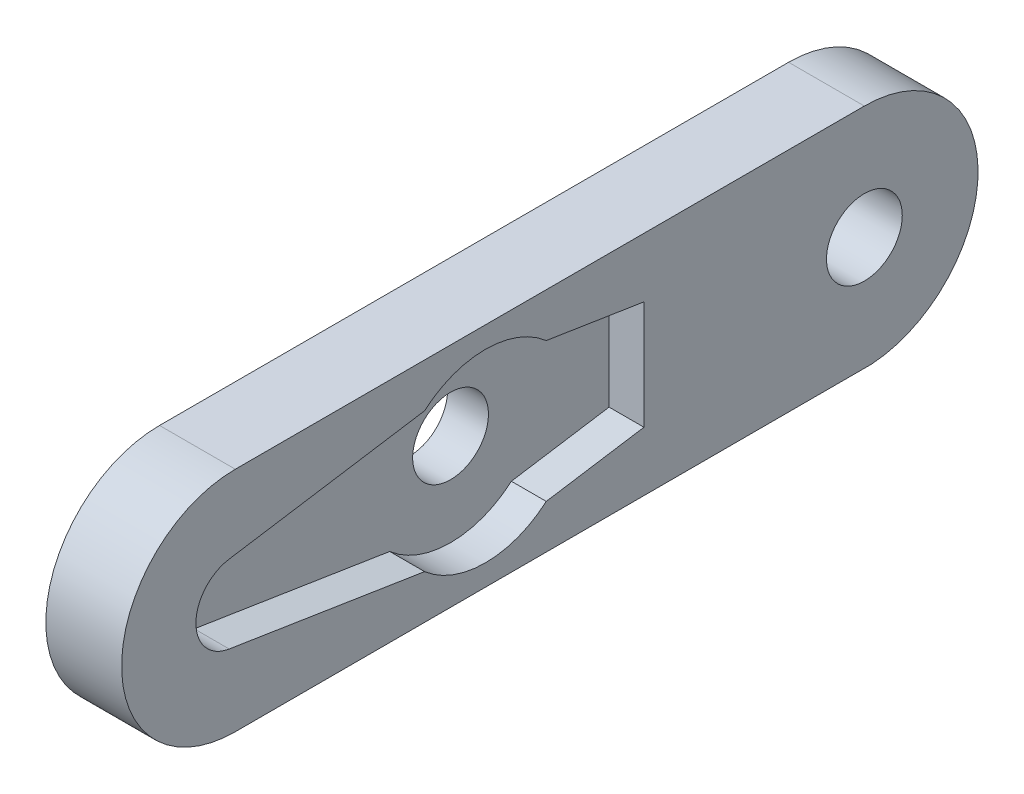
SolidWorks part; units mm, degrees
note: The reader was unsure of these and kept them because the rebuilt part matched: shared geometry of "Sketch4<3>".
ref_plane "Front Plane" through (0, 0, 0) normal (0, 0, 1) x (1, 0, 0)
ref_plane "Top Plane" through (0, 0, 0) normal (0, 1, 0) x (1, 0, 0)
ref_plane "Right Plane" through (0, 0, 0) normal (1, 0, 0) x (0, 0, -1)
sketch "Sketch1" plane through (0, 0, 0) normal (1, 0, 0) x (0, 0, -1)
  line L4 (10.4582, 3.5814) -> (4.0128, 4.5943)
  line L5 (-4.0128, 4.5943) -> (-16.9036, 2.5685)
  line L6 (-16.9036, -2.5685) -> (-4.0128, -4.5943)
  line L7 (4.0128, -4.5943) -> (10.4582, -3.5814)
  line L8 (0, 0) -> (20, 0)
  line L9 (10.4582, 3.5814) -> (10.4582, -3.5814)
  line L10 (-16.5, 7.5) -> (20, 7.5)
  line L11 (-16.5, -7.5) -> (20.4815, -7.4845)
  arc A4 (4.0128, 4.5943) -> (-4.0128, 4.5943) centre (0, 0) ccw
  arc A5 (-16.9036, 2.5685) -> (-16.9036, -2.5685) centre (-16.5, 0) ccw
  arc A6 (-4.0128, -4.5943) -> (4.0128, -4.5943) centre (0, 0) ccw
  circle A8 centre (20, 0) radius 2.5
  circle A9 centre (20, 0) radius 7.5
  arc A10 (-16.5, 7.5) -> (-9.954, -3.6606) centre (-16.5, 0) ccw
  dimension "D1" = 5
extrude "Boss-Extrude1" add sketch "Sketch1" along normal blind 2.3
sketch "Sketch2" plane through (0, 0, 0) normal (-1, 0, 0) x (0, 0, 1)
  line L2 (16.5, 7.5) -> (-20, 7.5)
  line L3 (-20.4815, -7.4845) -> (16.5, -7.5)
  line L4 (16.5, 7.5) -> (-20, 7.5)
  line L5 (-20.4815, -7.4845) -> (16.5, -7.5)
  circle A0 centre (-20, 0) radius 2.5 construction
  circle A1 centre (-20, 0) radius 2.5
  arc A2 (16.5, -7.5) -> (16.5, 7.5) centre (16.5, 0) ccw
  arc A3 (-20, 7.5) -> (-20.4815, -7.4845) centre (-20, 0) ccw
  arc A4 (16.5, -7.5) -> (16.5, 7.5) centre (16.5, 0) ccw
  arc A5 (-20, 7.5) -> (-20.4815, -7.4845) centre (-20, 0) ccw
  dimension "D1" = 0
extrude "Boss-Extrude2" add sketch "Sketch2" along normal blind 2.7
sketch "Sketch3" plane through (0, 0, 0) normal (1, 0, 0) x (0, 0, -1)
  circle A0 centre (0, 0) radius 2.5
extrude "Cut-Extrude1" cut sketch "Sketch3" against normal blind 10
sketch "Sketch4" plane through (2.3, 0, 0) normal (1, 0, 0) x (0, 0, -1)
  line L0 (20, 0) -> (25, 0)
  line L1 (25, 7.5) -> (20, 7.5)
  line L2 (25.4815, -7.4845) -> (20.4815, -7.4845)
  circle A0 centre (20, 0) radius 2.5 construction
  arc A1 (20.4815, -7.4845) -> (20, 7.5) centre (20, 0) ccw construction
  circle A2 centre (20, 0) radius 2.5
  arc A3 (20.4815, -7.4845) -> (20, 7.5) centre (20, 0) ccw
  circle A4 centre (25, 0) radius 2.5
  arc A5 (25.4815, -7.4845) -> (25, 7.5) centre (25, 0) ccw
extrude "Boss-Extrude3" add sketch "Sketch4" against normal blind 5
extrude "Cut-Extrude2" cut sketch "Sketch4<3>" against normal blind 5
sketch "Sketch4<3>" plane through (2.3, 0, 0) normal (1, 0, 0) x (0, 0, -1) same geometry as "Sketch4"
